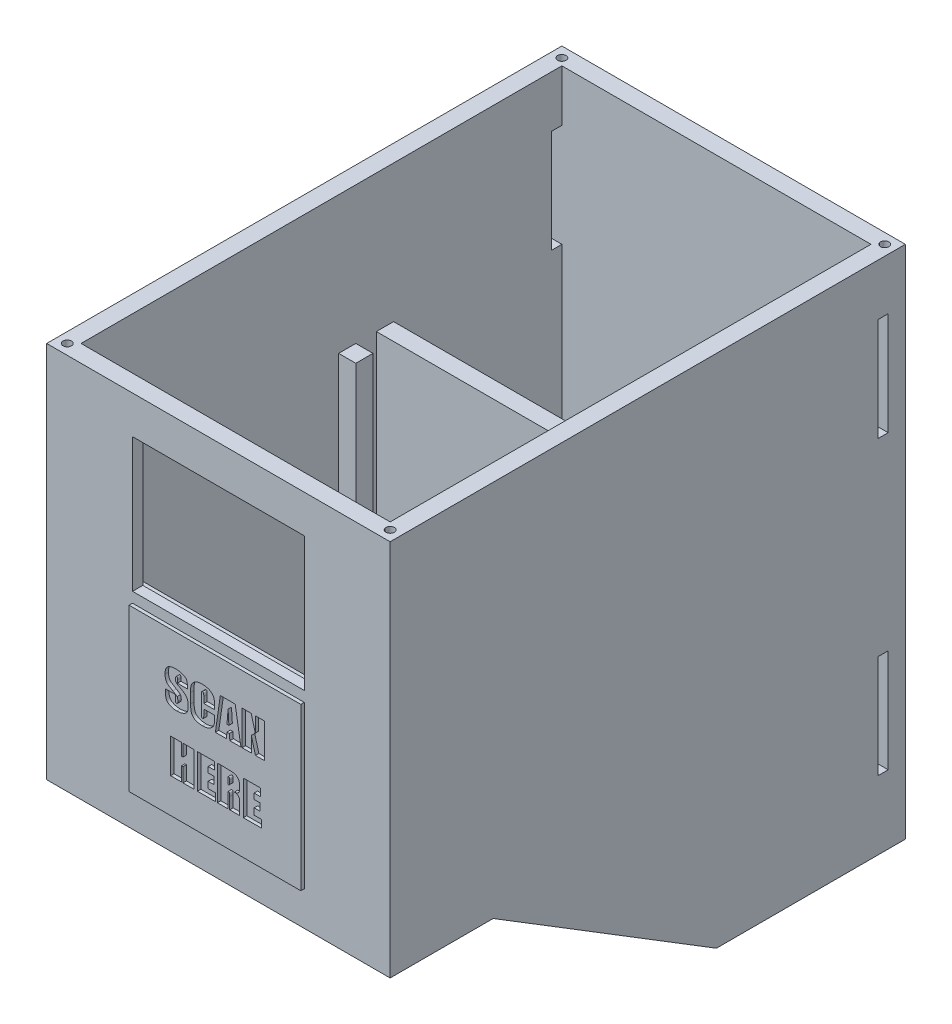
SolidWorks part; units mm, degrees
ref_plane "Front Plane" through (0, 0, 0) normal (0, 0, 1) x (1, 0, 0)
ref_plane "Top Plane" through (0, 0, 0) normal (0, 1, 0) x (1, 0, 0)
ref_plane "Right Plane" through (0, 0, 0) normal (1, 0, 0) x (0, 0, -1)
sketch "Sketch1" plane through (0, 0, 0) normal (0, 1, 0) x (1, 0, 0)
  line L1 (-50, -75) -> (50, -75)
  line L2 (-50, -75) -> (-50, 75)
  line L3 (-50, 75) -> (50, 75)
  line L4 (50, -75) -> (50, 75)
  line L5 (-50, -75) -> (50, 75) construction
  line L6 (-50, 75) -> (50, -75) construction
  point P0 (0, 0)
  dimension "D1" = 100
  dimension "D2" = 150
extrude "Boss-Extrude1" add sketch "Sketch1" along normal blind 150
sketch "Sketch13" plane through (50, 0, 0) normal (1, 0, 0) x (0, 0, -1)
  line L0 (-45, 40) -> (20, 0)
  line L1 (-75, 0) -> (-45, 0)
  line L2 (-75, 0) -> (-75, 40)
  line L3 (-75, 40) -> (-45, 40)
  line L5 (-75, 0) -> (75, 0) construction
  line L8 (-45, 0) -> (20, 0)
  dimension "D1" = 30
  dimension "D2" = 40
  dimension "D3" = 55
extrude "Cut-Extrude7" cut sketch "Sketch13" against normal up to next
shell "Shell1" thickness 5 removed face at (0, 150, 0)
sketch "Sketch3" plane through (0, 0, 0) normal (0, -1, 0) x (1, 0, 0)
  line L1 (50, 45) -> (50, 75) construction
  circle A0 centre (0, 60) radius 4
  circle A1 centre (-5, 50) radius 1.5
  circle A2 centre (5, 50) radius 1.5
  dimension "D3" = 8
  dimension "D4" = 3
  dimension "D5" = 10
  dimension "D7" = 10
  dimension "D8" = 5
  dimension "D1" = 60
  dimension "D2" = 50
extrude "Cut-Extrude2" cut sketch "Sketch3" against normal up to next
sketch "Sketch5" plane through (0, 0, 75) normal (0, 0, 1) x (1, 0, 0)
  line L0 (50, 150) -> (50, 40) construction
  line L1 (-25, 50) -> (25, 50)
  line L2 (-25, 50) -> (-25, 97)
  line L3 (-25, 97) -> (25, 97)
  line L4 (25, 50) -> (25, 97)
  line L5 (-25, 50) -> (25, 97) construction
  line L6 (-25, 97) -> (25, 50) construction
  line L7 (-50, 150) -> (50, 150) construction
  point P0 (0, 73.5)
  dimension "D1" = 50
  dimension "D2" = 47
  dimension "D3" = 50
  dimension "D4" = 76.5
extrude "Boss-Extrude3" add sketch "Sketch5" along normal blind 1
sketch "Sketch8" plane through (0, 0, 75) normal (0, 0, 1) x (1, 0, 0)
  line L0 (-50, 150) -> (-50, 40) construction
  line L1 (-25, 100) -> (25, 100)
  line L2 (-25, 100) -> (-25, 139)
  line L3 (-25, 139) -> (25, 139)
  line L4 (25, 100) -> (25, 139)
  line L5 (-25, 100) -> (25, 139) construction
  line L6 (-25, 139) -> (25, 100) construction
  line L7 (-50, 150) -> (50, 150) construction
  point P0 (0, 119.5)
  dimension "D1" = 50
  dimension "D2" = 39
  dimension "D3" = 50
  dimension "D4" = 50
extrude "Cut-Extrude3" cut sketch "Sketch8" against normal up to next
sketch "Sketch18" plane through (0, 0, 70) normal (0, 0, -1) x (-1, 0, 0)
  line L0 (-25, 139) -> (25, 139) construction
  line L1 (30, 99) -> (-26, 99)
  line L2 (30, 99) -> (30, 140)
  line L3 (30, 140) -> (-26, 140)
  line L4 (-26, 99) -> (-26, 140)
  line L6 (-25, 100) -> (-25, 139) construction
  line L7 (25, 139) -> (25, 100) construction
  dimension "D1" = 1
  dimension "D2" = 41
  dimension "D3" = 1
  dimension "D4" = 5
extrude "Cut-Extrude9" cut sketch "Sketch18" against normal blind 2
sketch "Sketch20" plane through (0, 0, 76) normal (0, 0, 1) x (1, 0, 0)
  line L0 (25, 97) -> (-25, 97) construction
  line L1 (-23, 96) -> (23, 96)
  line L2 (-23, 96) -> (-23, 51)
  line L3 (-23, 51) -> (23, 51)
  line L4 (23, 96) -> (23, 51)
  line L5 (-25, 50) -> (25, 50) construction
  line L6 (25, 50) -> (25, 97) construction
  line L7 (-25, 97) -> (-25, 50) construction
  dimension "D1" = 1
  dimension "D2" = 1
  dimension "D3" = 2
  dimension "D4" = 2
extrude "Cut-Extrude10" cut sketch "Sketch20" against normal blind 15 from offset 4 offset against normal yes
sketch "Sketch21" plane through (0, 45, 0) normal (0, 1, 0) x (1, 0, 0)
  line L1 (9, -52.5) -> (-9, -52.5)
  line L2 (9, -52.5) -> (9, -37.5)
  line L3 (9, -37.5) -> (-9, -37.5)
  line L4 (-9, -52.5) -> (-9, -37.5)
  circle A0 centre (5, -50) radius 1.5 construction
  circle A1 centre (-5, -50) radius 1.5 construction
  dimension "D3" = 4
  dimension "D1" = 4
  dimension "D2" = 2.5
  dimension "D4" = 15
extrude "Cut-Extrude11" cut sketch "Sketch21" against normal blind 2.5
sketch "Sketch22" plane through (-45, 0, 0) normal (1, 0, 0) x (0, 0, -1)
  line L0 (70, 150) -> (-70, 150) construction
  line L5 (70, 150) -> (70, 5) construction
  line L7 (-43.5848, 45) -> (21.4152, 5) construction
  line L8 (10, 150) -> (10, 12.0247)
  line L11 (10, 150) -> (5, 150)
  line L14 (5, 150) -> (5, 15.1017)
  line L15 (5, 15.1017) -> (10, 12.0247)
  dimension "D1" = 60
  dimension "D3" = 5
extrude "Boss-Extrude6" add sketch "Sketch22" along normal blind 5
mirror "Mirror2" about plane through (0, 0, 0) normal (1, 0, 0) of "Boss-Extrude6"
sketch "Sketch23" plane through (-45, 0, 0) normal (1, 0, 0) x (0, 0, -1)
  line L0 (16, 150) -> (21, 150)
  line L1 (70, 150) -> (10, 150) construction
  line L3 (21, 150) -> (21, 5.2555)
  line L4 (21, 5.2555) -> (16, 8.3324)
  line L6 (10, 12.0247) -> (10, 150) construction
  line L7 (16, 150) -> (16, 8.3324)
  line L8 (10, 12.0247) -> (21.4152, 5) construction
  dimension "D1" = 6
  dimension "D2" = 5
extrude "Boss-Extrude7" add sketch "Sketch23" along normal up to next
sketch "Sketch24" plane through (-45, 0, 0) normal (1, 0, 0) x (0, 0, -1)
  line L0 (70, 150) -> (70, 5) construction
  line L1 (70, 135) -> (67, 135)
  line L2 (70, 135) -> (70, 105)
  line L3 (70, 105) -> (67, 105)
  line L4 (67, 135) -> (67, 105)
  line L5 (70, 150) -> (21, 150) construction
  line L6 (70, 5) -> (21.4152, 5) construction
  line L7 (70, 20) -> (67, 20)
  line L8 (70, 20) -> (70, 50)
  line L9 (70, 50) -> (67, 50)
  line L10 (67, 20) -> (67, 50)
  dimension "D1" = 15
  dimension "D2" = 30
  dimension "D3" = 3
  dimension "D4" = 15
extrude "Cut-Extrude12" cut sketch "Sketch24" against normal through all both and the other way through all
sketch "Sketch28" plane through (0, 0, 76) normal (0, 0, 1) x (1, 0, 0)
  line L0 (-25, 73.5) -> (25, 73.5) construction
  line L1 (-25, 97) -> (-25, 50) construction
  line L2 (25, 50) -> (25, 97) construction
  line L3 (-25, 77.511) -> (25, 77.511) construction
  text T0 "SCAN\r\nHERE" font "Impact" height 10
extrude "Cut-Extrude14" cut sketch "Sketch28" against normal blind 1
sketch "Sketch30" plane through (0, 0, -75) normal (0, 0, -1) x (-1, 0, 0)
  text T0 "IBE VAN DE VEIRE\r\nSTEF GIELEN" font "Comic Sans MS" height 5
extrude "Cut-Extrude16" cut sketch "Sketch30" against normal blind 1
sketch "Sketch32" plane through (0, 150, 0) normal (0, 1, 0) x (1, 0, 0)
  line L0 (-50, 75) -> (-50, -75) construction
  line L1 (50, 75) -> (-50, 75) construction
  line L2 (-50, -75) -> (50, -75) construction
  line L3 (50, -75) -> (50, 75) construction
  circle A0 centre (-47, 72) radius 1.225
  circle A1 centre (-47, -72) radius 1.225
  circle A2 centre (47, -72) radius 1.225
  circle A3 centre (47, 72) radius 1.225
  dimension "D1" = 2.45
  dimension "D2" = 3
  dimension "D3" = 3
  dimension "D4" = 2.45
  dimension "D5" = 3
  dimension "D6" = 3
  dimension "D7" = 2.45
  dimension "D8" = 3
  dimension "D9" = 3
  dimension "D10" = 2.45
  dimension "D11" = 3
  dimension "D12" = 3
extrude "Cut-Extrude17" cut sketch "Sketch32" against normal blind 20
sketch "Sketch33" plane through (0, 150, 0) normal (0, 1, 0) x (1, 0, 0)
  line L1 (-45, 5) -> (45, 5)
  line L2 (-45, 5) -> (-45, 21)
  line L3 (-45, 21) -> (45, 21)
  line L4 (45, 5) -> (45, 21)
extrude "Cut-Extrude18" cut sketch "Sketch33" against normal blind 40
sketch "Sketch34" plane through (0, 150, 0) normal (0, 1, 0) x (1, 0, 0)
  line L0 (50, 75) -> (-50, 75) construction
  line L1 (-45, 75) -> (50, 75)
  line L2 (-45, 75) -> (-45, -75)
  line L3 (-45, -75) -> (50, -75)
  line L4 (50, 75) -> (50, -75)
